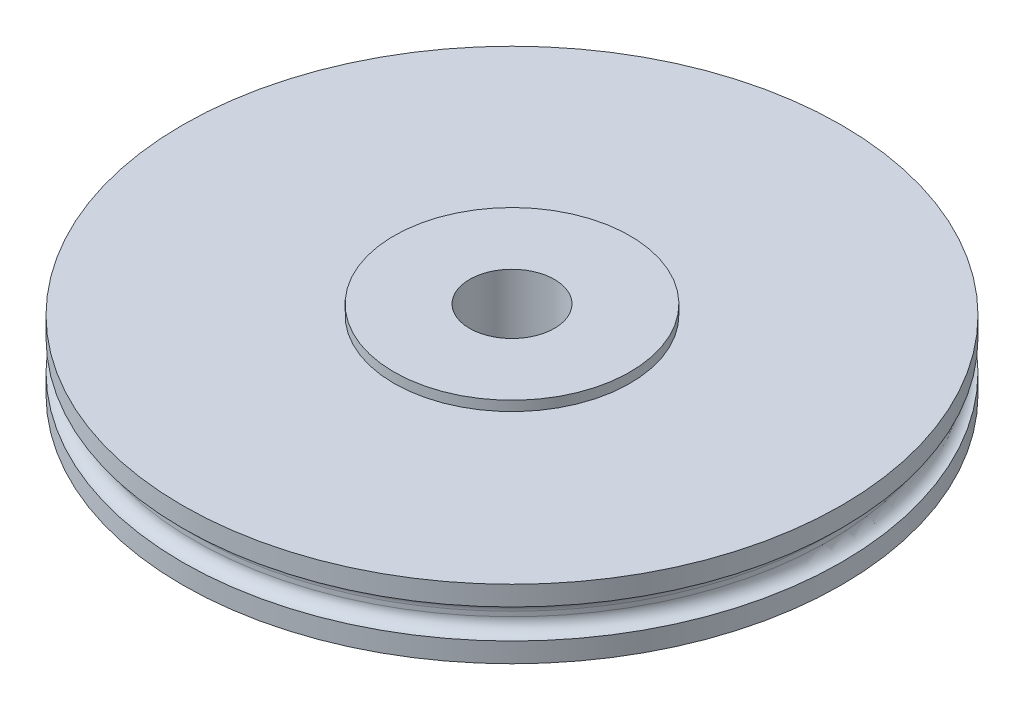
SolidWorks part; units mm, degrees
ref_plane "Front Plane" through (0, 0, 0) normal (0, 0, 1) x (1, 0, 0)
ref_plane "Top Plane" through (0, 0, 0) normal (0, 1, 0) x (1, 0, 0)
ref_plane "Right Plane" through (0, 0, 0) normal (1, 0, 0) x (0, 0, -1)
sketch "Sketch1" plane through (0, 0, 0) normal (0, 1, 0) x (1, 0, 0)
  circle A0 centre (0, 0) radius 26.5906
  dimension "D1" = 53.1812
extrude "Boss-Extrude1" add sketch "Sketch1" along normal blind 1.5875
sketch "Sketch2" plane through (0, 1.5875, 0) normal (0, 1, 0) x (1, 0, 0)
  circle A0 centre (0, 0) radius 25.5984
  dimension "D1" = 51.1969
extrude "Boss-Extrude2" add sketch "Sketch2" along normal blind 2.3813
sketch "Sketch3" plane through (0, 3.9688, 0) normal (0, 1, 0) x (1, 0, 0)
  circle A0 centre (0, 0) radius 26.5906
extrude "Boss-Extrude3" add sketch "Sketch3" along normal blind 1.5875
sketch "Sketch5" plane through (0, 5.5563, 0) normal (0, 1, 0) x (1, 0, 0)
  circle A0 centre (0, 0) radius 9.525
extrude "Boss-Extrude4" add sketch "Sketch5" along normal blind 0.7937
sketch "Sketch6" plane through (0, 6.35, 0) normal (0, 1, 0) x (1, 0, 0)
  circle A0 centre (0, 0) radius 3.425
  dimension "D1" = 6.85
extrude "Cut-Extrude1" cut sketch "Sketch6" against normal through all
fillet "Fillet1" radius 1 1 edges at (0, 1.5875, 25.5984)
fillet "Fillet2" radius 1 1 edges at (0, 3.9688, 25.5984)
